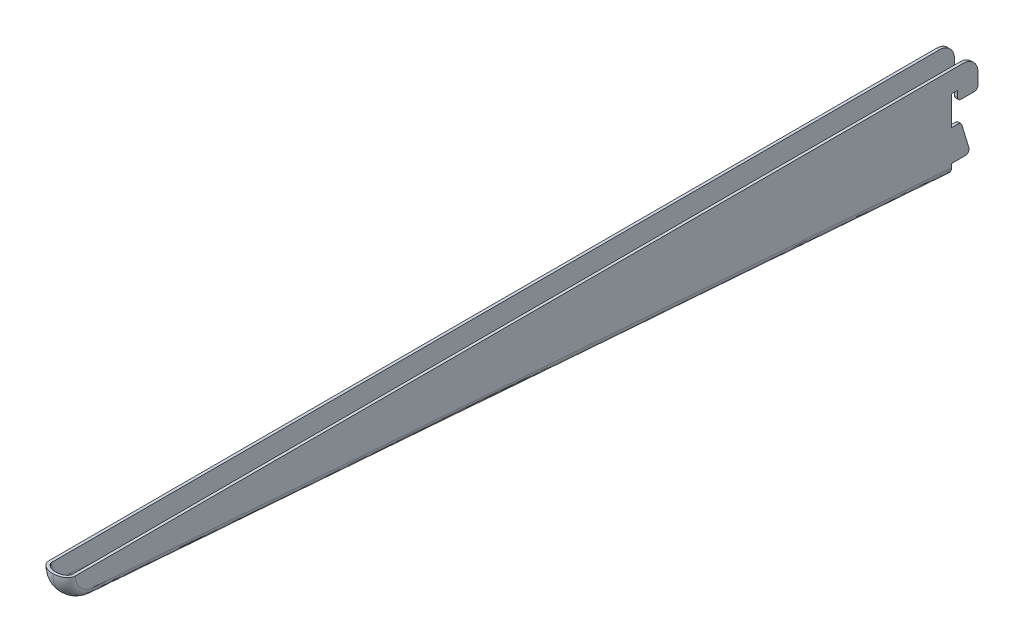
SolidWorks part; units mm, degrees
ref_plane "Front Plane" through (0, 0, 0) normal (0, 0, 1) x (1, 0, 0)
ref_plane "Top Plane" through (0, 0, 0) normal (0, 1, 0) x (1, 0, 0)
ref_plane "Right Plane" through (0, 0, 0) normal (1, 0, 0) x (0, 0, -1)
sketch "Sketch1" plane through (0, 0, 0) normal (1, 0, 0) x (0, 0, -1)
  line L0 (0, 0) -> (0, 50)
  line L1 (0, 50) -> (-470, 50)
  line L3 (-456.149, 35.0441) -> (0, 0)
  line L4 (10, 7) -> (5, 23.5)
  line L5 (5, 23.5) -> (0, 23.5)
  line L6 (10, 7) -> (0, 7)
  line L7 (0, 39) -> (3, 39)
  line L8 (3, 39) -> (3, 34)
  line L9 (3, 34) -> (14, 34)
  line L10 (14, 34) -> (14, 50)
  line L11 (14, 50) -> (0, 50)
  arc A0 (-470, 50) -> (-456.149, 35.0441) centre (-455, 50) ccw
  dimension "D10" = 15
  dimension "D1" = 470
  dimension "D2" = 50
  dimension "D3" = 7
  dimension "D4" = 16.5
  dimension "D5" = 5
  dimension "D6" = 3
  dimension "D7" = 5
  dimension "D8" = 11
  dimension "D9" = 11
  dimension "D11" = 10
extrude "Boss-Extrude1" add sketch "Sketch1" along normal blind 7 contours L1 A0 L3 L0 region at (0, 32.3087, 189.9871)
fillet "Fillet1" radius 7 2 edges at (7, 39.8077, 466.0053) (7, 17.522, 228.0745) second distance 5 first distance on face at (3.5, 41.1649, 464.5399) first distance on face at (3.5, 17.522, 228.0745)
shell "Shell1" thickness 1.5 removed face at (4.375, 15.0074, 0) removed face at (2.625, 50, 117.4999) removed face at (0, 33.761, 231.5372)
extrude "Boss-Extrude2" add sketch "Sketch1<4>" along normal up to surface (7 mm away) from surface contours L6 L4 L0 | L10 L11 L0 L7 L8 L9 region at (0, 14.3333, -3.8889) region at (0, 42.3947, -7.3947) up to face at (7, 36.261, 230.1914) starting at face at (5.5, 36.261, 230.1914)
sketch "Sketch1<4>" plane through (0, 0, 0) normal (1, 0, 0) x (0, 0, -1) same geometry as "Sketch1"
fillet "Fillet2" radius 8 1 edges at (6.25, 50, -14)
fillet "Fillet3" radius 2 4 edges at (6.25, 7, -10) (6.25, 34, -3) (6.25, 34, -14) (6.25, 23.5, -5)
mirror "Mirror5" about plane through (0, 0, 0) normal (1, 0, 0) of bodies 102
